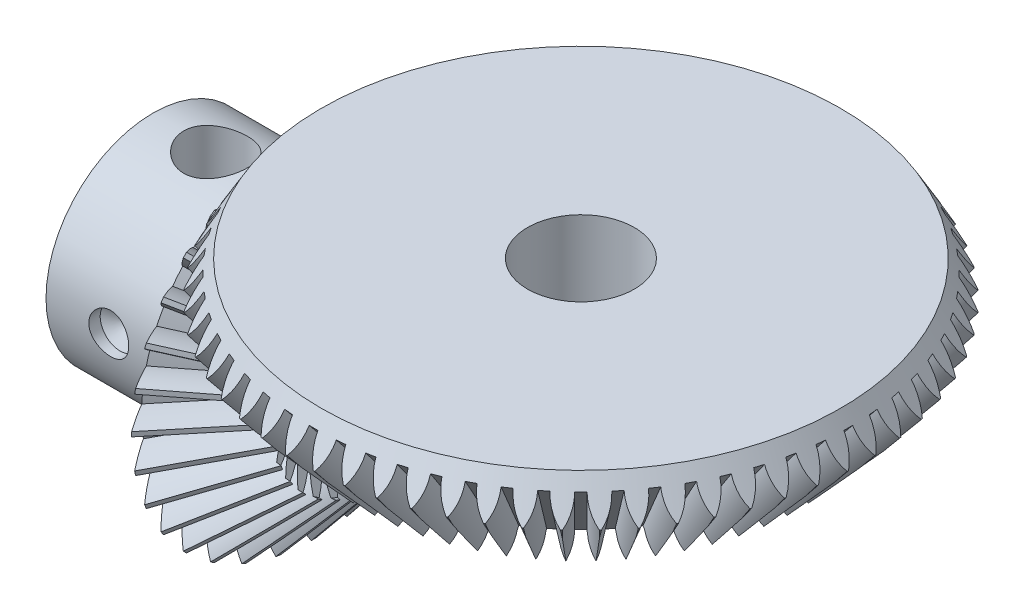
SolidWorks part; units mm, degrees
ref_plane "Front Plane" through (0, 0, 0) normal (0, 0, 1) x (1, 0, 0)
ref_plane "Top Plane" through (0, 0, 0) normal (0, 1, 0) x (1, 0, 0)
ref_plane "Right Plane" through (0, 0, 0) normal (1, 0, 0) x (0, 0, -1)
sketch "Sketch1" plane through (0, 0, 0) normal (0, 0, 1) x (1, 0, 0)
  line L0 (-4.7625, 14.2748) -> (-2.3787, 14.2748)
  line L1 (-2.3787, 14.2748) -> (-2.3787, 4.6228)
  line L2 (-19.05, 2.3787) -> (-19.05, 4.7625)
  line L3 (-19.05, 4.7625) -> (-13.462, 4.7625)
  line L4 (0, 19.9421) -> (0, -19.9421) construction
  line L5 (-20.2254, 0) -> (20.2254, 0) construction
  line L6 (-19.05, 2.3787) -> (-10.2922, 2.3787)
  line L7 (0, 0) -> (-12.4337, 7.1786) construction
  line L8 (0, 0) -> (15.0111, 8.6667) construction
  line L9 (-4.7625, 14.2748) -> (-4.7625, 8.6868)
  line L10 (-4.7625, 8.6868) -> (-11.5629, 8.6868)
  line L13 (-9.2166, 4.6228) -> (-2.3787, 4.6228)
  line L14 (-16.256, 5.1537) -> (-16.256, 2.4592) construction
  line L15 (-12.4337, 7.1786) -> (-12.4337, -7.1786) construction
  line L16 (-12.4337, -7.1786) -> (0, 0) construction
  line L17 (-12.5125, 7.0422) -> (-9.7544, 3.6913) construction
  line L18 (-13.462, 4.7625) -> (-13.462, 5.3975)
  line L19 (-13.462, 5.3975) -> (-11.5629, 8.6868)
  line L20 (-10.2922, 2.3787) -> (-10.2922, 2.7597)
  line L21 (-10.2922, 2.7597) -> (-9.2166, 4.6228)
  point P2 (-8.9142, 5.1466)
  dimension "Length [YY]" = 14.2748
  dimension "Length [XX]" = 19.05
  dimension "Bore [BOR]" = 4.7574
  dimension "D1" = 4.7574
  dimension "D2" = 30
  dimension "D3" = 9.525
  dimension "Diameter [SD4]" = 9.525
  dimension "D4" = 2.794
  dimension "D6" = 5.588
  dimension "D8" = 2.3838
  dimension "D7" = 4.064
  dimension "D9" = 0.635
  dimension "D10" = 60
  dimension "D5" = 4.064
  dimension "D11" = 0.381
sketch "Sketch2" plane through (0, 0, 0) normal (0, 0, 1) x (1, 0, 0)
  line L0 (-4.7625, 14.2748) -> (-2.3787, 14.2748) construction
  line L1 (-4.7625, 14.2748) -> (-4.7625, 8.6868) construction
  line L2 (-4.7625, 8.6868) -> (-11.5629, 8.6868) construction
  line L3 (-2.3787, 14.2748) -> (-2.3787, 4.6228) construction
  line L4 (-9.2166, 4.6228) -> (-2.3787, 4.6228) construction
  line L6 (-12.5125, 7.0422) -> (-9.7544, 3.6913) construction
  line L8 (-4.7625, 14.2748) -> (-2.3787, 14.2748)
  line L9 (-4.7625, 14.2748) -> (-4.7625, 8.6868)
  line L10 (-4.7625, 8.6868) -> (-11.5629, 8.6868)
  line L11 (-2.3787, 14.2748) -> (-2.3787, 4.6228)
  line L12 (-9.2166, 4.6228) -> (-2.3787, 4.6228)
  line L13 (-9.7544, 3.6913) -> (-9.2166, 4.6228)
  line L14 (-12.5125, 7.0422) -> (-9.7544, 3.6913)
  line L15 (-11.5629, 8.6868) -> (-12.5125, 7.0422)
  line L16 (0, 19.9421) -> (0, -19.9421) construction
  line L17 (0, 19.9421) -> (0, -19.9421) construction
revolve "Revolve1-LargestGear" add sketch "Sketch2" angle 360 about L17
ref_plane "Plane1" through (-9.7544, 3.6913, 0) normal (0.6355, -0.7721, 0) x (0.7721, 0.6355, 0)
sketch "Sketch3" plane through (-9.7544, 3.6913, 0) normal (0.6355, -0.7721, 0) x (0.7721, 0.6355, 0)
  line L0 (1.143, 0) -> (0, 0) construction
  line L1 (13.208, 0) -> (0.5118, -0.3117) construction
  line L2 (0.5118, 0.3117) -> (0.873, 0.1802) construction
  line L3 (0.5118, 0.3117) -> (13.208, 0) construction
  line L4 (1.1446, 0.1948) -> (0.5097, 0.2051) construction
  line L5 (1.1446, 0.1948) -> (1.1366, -0.2963) construction
  line L6 (0, 0) -> (-0.254, 0) construction
  circle A0 centre (13.208, 0) radius 13.208 construction
  circle A1 centre (13.208, 0) radius 12.7 construction
  circle A2 centre (13.208, 0) radius 12.065 construction
  arc A3 (-0.2304, 0.7974) -> (1.1446, 0.1948) centre (1.1759, 2.1363) ccw
  arc A4 (-0.2304, -0.7974) -> (1.1446, -0.1948) centre (1.1759, -2.1363) cw
  arc A5 (1.1446, 0.1948) -> (1.1446, -0.1948) centre (13.208, 0) ccw
  arc A6 (-0.2304, 0.7974) -> (-0.2304, -0.7974) centre (13.208, 0) ccw
  ellipse E0 centre (7.5314, 0) end of major axis (7.5314, -9.7544) minor radius 7.5314 construction
  ellipse E1 centre (9.6609, 0) end of major axis (9.6609, -12.5125) minor radius 9.6609 construction
  ellipse E2 centre (9.6609, 0) end of major axis (9.6609, -12.5125) minor radius 9.6609 (0.018, 0.7627) -> (0.018, -0.7627) ccw construction
  dimension "Dimension [SD21]" = 26.416
  dimension "Pitch Diameter Largest Gear [PD1]" = 25.4
  dimension "D2" = 1.143
  dimension "D3" = 2.813
  dimension "D4" = 20
  dimension "D5" = 0.254
extrude "Cut-Extrude3-Teeth" cut sketch "Sketch3" against normal blind 10 and the other way through all
pattern_circular "CirPattern1" count 64 over 360 about axis through (0, 19.9421, 0) along (0, -1, 0) of "Cut-Extrude3-Teeth"
sketch "Sketch4" plane through (0, 0, 0) normal (0, 0, 1) x (1, 0, 0)
  line L0 (-20.2254, 0) -> (20.2254, 0) construction
  line L1 (-20.2254, 0) -> (20.2254, 0) construction
  line L2 (-12.5125, 7.0422) -> (-9.7544, 3.6913) construction
  line L3 (-12.5125, 7.0422) -> (-9.7544, 3.6913)
  line L4 (-13.462, 5.3975) -> (-11.5629, 8.6868) construction
  line L5 (-13.462, 4.7625) -> (-13.462, 5.3975) construction
  line L6 (-13.462, 5.3975) -> (-12.5125, 7.0422)
  line L7 (-13.462, 4.7625) -> (-13.462, 5.3975)
  line L8 (-10.2922, 2.7597) -> (-9.2166, 4.6228) construction
  line L10 (-19.05, 2.3787) -> (-10.2922, 2.3787) construction
  line L11 (-19.05, 2.3787) -> (-19.05, 4.7625) construction
  line L12 (-19.05, 4.7625) -> (-13.462, 4.7625) construction
  line L13 (-10.2922, 2.3787) -> (-10.2922, 2.7597) construction
  line L14 (-10.2922, 2.7597) -> (-9.7544, 3.6913)
  line L15 (-10.2922, 2.3787) -> (-10.2922, 2.7597)
  line L20 (-19.05, 2.3787) -> (-10.2922, 2.3787)
  line L21 (-19.05, 2.3787) -> (-19.05, 4.7625)
  line L22 (-19.05, 4.7625) -> (-13.462, 4.7625)
revolve "Revolve2-SmallestGear" add sketch "Sketch4" angle 360 about L1
sketch "Sketch5" plane through (-9.7544, 3.6913, 0) normal (0.6355, -0.7721, 0) x (0.7721, 0.6355, 0)
  line L0 (5.1856, 0) -> (0.0431, 0) construction
  line L1 (-1.7783, 0) -> (1.7783, 0) construction
  arc A0 (-1.2494, 0) -> (1.1426, 0.1016) centre (0.049, -2.3589) cw
  arc A1 (1.1426, 0.1016) -> (1.1426, -0.1016) centre (-10.922, 0) cw
  arc A2 (1.1426, -0.1016) -> (-1.2494, 0) centre (0.049, 2.3589) cw
  arc A5 (1.009, -0.2018) -> (0.1718, -0.4744) centre (1.1759, -2.1363) ccw construction
  arc A6 (1.1446, 0.1948) -> (1.1446, -0.1948) centre (13.208, 0) ccw construction
  arc A8 (0.1718, 0.4744) -> (1.009, 0.2018) centre (1.1759, 2.1363) ccw construction
  ellipse E0 centre (-2.7611, 0) end of major axis (-2.7611, 2.3787) minor radius 1.5117 construction
  point P24 (1.143, 0)
  dimension "D1" = 0.2032
extrude "Extrude1-Teeth" add sketch "Sketch5" against normal blind 5.842 and the other way blind 2.54
pattern_circular "CirPattern2" count 32 over 360 about axis through (0, 0, 0) along (1, 0, 0) of "Extrude1-Teeth"
sketch "Sketch6" plane through (0, 0, 0) normal (0, 0, 1) x (1, 0, 0)
  line L0 (-13.462, 4.7625) -> (-13.462, 5.3975) construction
  line L1 (-19.05, 4.7625) -> (-13.462, 4.7625) construction
  line L2 (-10.2922, 2.3787) -> (-10.2922, 2.7597) construction
  line L3 (-4.7625, 8.6868) -> (-11.5629, 8.6868) construction
  line L4 (-4.7625, 14.2748) -> (-4.7625, 8.6868) construction
  line L5 (-13.462, 4.7625) -> (-13.462, 5.3975)
  line L6 (-13.462, 5.3975) -> (-11.5629, 8.6868) construction
  line L7 (-9.2166, 4.6228) -> (-2.3787, 4.6228) construction
  line L9 (-19.05, 2.3787) -> (-10.2922, 2.3787) construction
  line L10 (-20.2254, 0) -> (20.2254, 0) construction
  line L11 (-19.05, 4.7625) -> (-13.462, 4.7625)
  line L12 (-13.462, 5.3975) -> (-11.5629, 8.6868)
  line L13 (-4.7625, 8.6868) -> (-11.5629, 8.6868)
  line L14 (-4.7625, 11.4808) -> (-4.7625, 8.6868)
  line L15 (-19.05, 2.3787) -> (-19.05, 0)
  line L16 (0, 0) -> (0, 4.6228)
  line L17 (-9.2166, 4.6228) -> (0, 4.6228)
  line L19 (-19.05, 2.3787) -> (-10.2922, 2.3787)
  line L20 (-20.2254, 0) -> (20.2254, 0) construction
  line L21 (-19.05, 4.7625) -> (-19.05, 11.4808)
  line L22 (-19.05, 11.4808) -> (-4.7625, 11.4808)
  line L23 (-19.05, 0) -> (0, 0)
  line L24 (-19.05, 4.7625) -> (-19.05, -4.7625) construction
  line L25 (0, 19.9421) -> (0, -19.9421) construction
  line L26 (-10.2922, 2.7597) -> (-9.2166, 4.6228) construction
  line L27 (-10.2922, 2.3787) -> (-10.2922, 2.7597)
  line L28 (-10.2922, 2.7597) -> (-9.2166, 4.6228)
revolve "Cut-Revolve1" cut sketch "Sketch6" angle 360 about L20
ref_plane "Plane2" through (0, 4.7625, 0) normal (0, 1, 0) x (-1, 0, 0)
hole_wizard "#4-40 Tapped Hole1" positions "Sketch11" profile "Sketch10" tap size "#4-40" standard "Ansi Inch"
sketch "Sketch11" plane through (0, 4.7625, 0) normal (0, 1, 0) x (-1, 0, 0)
  line L0 (19.05, -4.7625) -> (19.05, 4.7625) construction
  point P0 (16.256, 0)
  dimension "D1" = 2.794
sketch "Sketch10" plane through (-16.256, 4.7625, 0) normal (1, 0, 0) x (0, 0, 1)
  line L0 (0, 0) -> (0, 4.4892)
  line L1 (0, 4.4892) -> (1.1303, 3.81)
  line L2 (1.1303, 3.81) -> (1.1303, 3.175)
  line L3 (1.1303, 3.175) -> (1.4224, 3.175)
  line L4 (1.4224, 3.175) -> (1.4224, 0)
  line L5 (1.4224, 0) -> (0, 0)
  line L10 (0, 4.4892) -> (-1.1303, 3.81) construction
  line L11 (0, -6.35) -> (0, 107.95) construction
  dimension "Tap Drill Dia." = 2.2606
  dimension "Tap Drill Depth" = 3.81
  dimension "Thread Major Dia." = 2.8448
  dimension "Thread Depth" = 3.175
  dimension "Drill Angle" = 118
ref_plane "Plane3" through (0, 0, 4.7625) normal (0, 0, 1) x (1, 0, 0)
hole_wizard "#50 (0.07) Diameter Hole1" positions "Sketch13" profile "Sketch12" hole size "#50" standard "Ansi Inch"
sketch "Sketch13" plane through (0, 0, 4.7625) normal (0, 0, 1) x (1, 0, 0)
  line L0 (-19.05, 4.7625) -> (-19.05, -4.7625) construction
  point P0 (-16.256, 0)
  dimension "D1" = 2.794
sketch "Sketch12" plane through (-16.256, 0, 4.7625) normal (1, 0, 0) x (0, -1, 0)
  line L0 (0, 0) -> (0, 1.0422)
  line L1 (0, 1.0422) -> (0.889, 0.508)
  line L2 (0.889, 0.508) -> (0.889, 0)
  line L5 (0.889, 0) -> (0, 0)
  line L10 (0, 1.0422) -> (-0.889, 0.508) construction
  line L11 (0, -6.35) -> (0, 107.95) construction
  dimension "Hole Dia." = 1.778
  dimension "Hole Depth" = 0.508
  dimension "Drill Angle" = 118
sketch "Sketch14" plane through (0, 14.2748, 0) normal (0, 1, 0) x (-1, 0, 0)
  circle A0 centre (0, 0) radius 6.4882
extrude "Cut-Extrude1" cut sketch "Sketch14" against normal blind 5.588
equation "\"D1@Sketch1\" = \"Bore [BOR]@Sketch1\""
equation "\"D3@Sketch1\" = \"Diameter [SD4]@Sketch1\""
equation "\"D2@Sketch3\" = (\"Dimension [SD21]@Sketch3\"-\"Pitch Diameter Largest Gear [PD1]@Sketch3\")*1.125"
equation "\"D3@Sketch3\" = 180/\"Number of Teeth Largest Gear [NOF1]@CirPattern1\""
